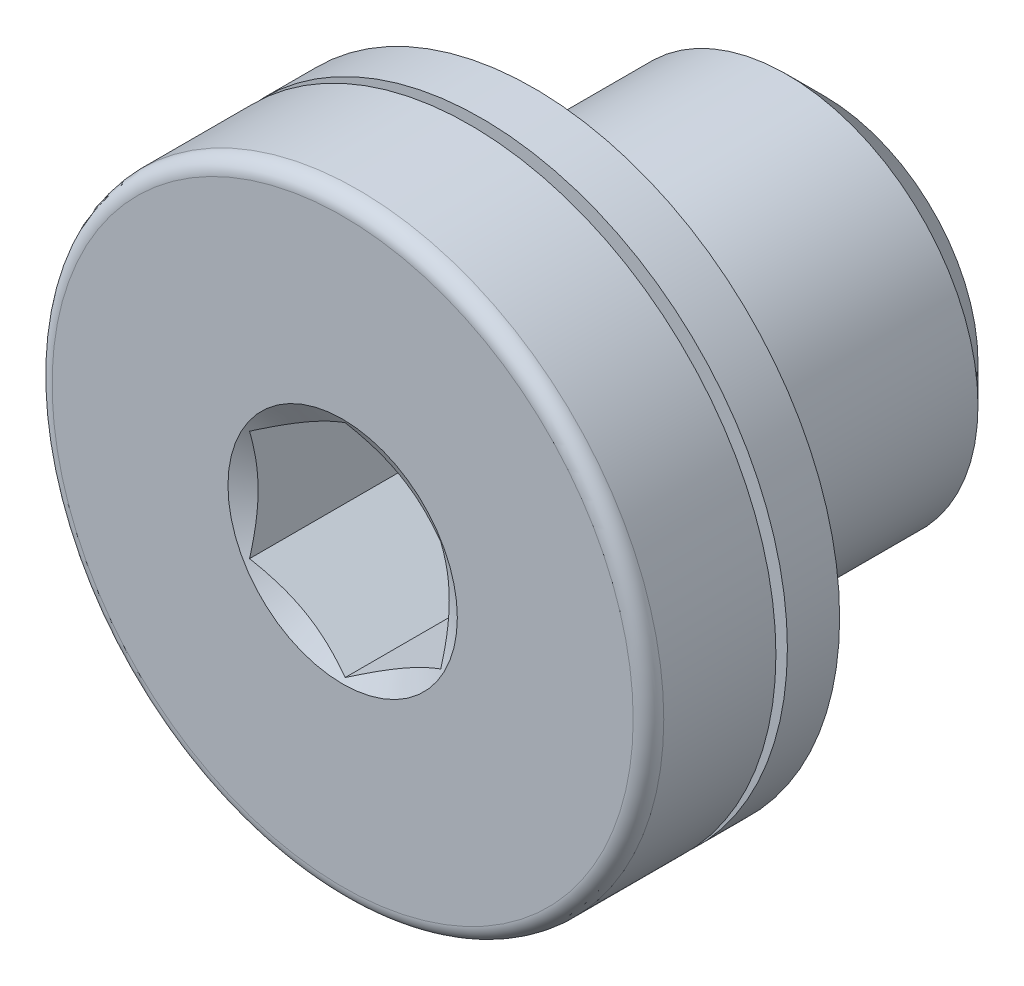
SolidWorks part; units mm, degrees
ref_plane "Ebene vorne" through (0, 0, 0) normal (0, 0, 1) x (1, 0, 0)
ref_plane "Ebene oben" through (0, 0, 0) normal (0, 1, 0) x (1, 0, 0)
ref_plane "Ebene rechts" through (0, 0, 0) normal (1, 0, 0) x (0, 0, -1)
sketch "Skizze1" plane through (0, 0, 0) normal (1, 0, 0) x (0, 0, -1)
  line L0 (-1.634, 0) -> (-2.5, 1.5)
  line L1 (-2.5, 1.5) -> (-2.5, 3.8)
  line L2 (-2.3, 4) -> (-0.8333, 4)
  line L3 (-0.8333, 4) -> (-0.8333, 3.6)
  line L4 (-0.8333, 3.6) -> (-0.6833, 3.6)
  line L5 (-0.6833, 3.6) -> (-0.6833, 4)
  line L6 (-0.6833, 4) -> (0, 4)
  line L7 (0, 4) -> (0, 2.0095)
  line L8 (0, 2.0095) -> (0.4905, 2.5)
  line L9 (0.4905, 2.5) -> (3.3095, 2.5)
  line L10 (3.3095, 2.5) -> (3.8, 2.0095)
  line L11 (3.8, 2.0095) -> (3.8, 0)
  line L12 (3.8, 0) -> (-1.634, 0)
  line L13 (3.8, 0) -> (-1.634, 0) construction
  arc A0 (-2.5, 3.8) -> (-2.3, 4) centre (-2.3, 3.8) cw
revolve "Rotation1" add sketch "Skizze1" angle 360 about L13 reverse direction yes
cosmetic thread "Gewindedarstellung1" parameters "D1"=3.8, "D2"=4.019
ref_plane "Ebene1" through (0, 0, 2.5) normal (0, 0, 1) x (1, 0, 0)
sketch "Skizze2" plane through (0, 0, 2.5) normal (0, 0, 1) x (1, 0, 0)
  line L0 (-1.25, -0.7217) -> (0, -1.4434)
  line L1 (0, -1.4434) -> (1.25, -0.7217)
  line L2 (1.25, -0.7217) -> (1.25, 0.7217)
  line L3 (1.25, 0.7217) -> (0, 1.4434)
  line L4 (0, 1.4434) -> (-1.25, 0.7217)
  line L5 (-1.25, 0.7217) -> (-1.25, -0.7217)
extrude "Schnitt-Linear austragen1" cut sketch "Skizze2" against normal blind 2.5
ref_plane "ANBAU XY" through (0, 0, 0) normal (0, 0, 1) x (1, 0, 0)
ref_plane "ANBAU XZ" through (0, 0, 0) normal (0, -1, 0) x (-1, 0, 0)
ref_plane "ANBAU YZ" through (0, 0, 0) normal (1, 0, 0) x (0, 0, -1)
ref_axis "ANBAU X" through (-80.9, 0, 0) along (1, 0, 0)
ref_axis "ANBAU Y" through (0, -50, 0) along (0, 1, 0)
ref_axis "ANBAU Z" through (0, 0, 80.9) along (0, 0, -1)
sketch3d "ANBAU"
  point P0 (0, 0, 0)
ref_plane "ANBAU_STD XY" through (0, 0, 0) normal (0, 0, 1) x (1, 0, 0)
ref_plane "ANBAU_STD XZ" through (0, 0, 0) normal (0, -1, 0) x (-1, 0, 0)
ref_plane "ANBAU_STD YZ" through (0, 0, 0) normal (1, 0, 0) x (0, 0, -1)
ref_axis "ANBAU_STD X" through (-80.9, 0, 0) along (1, 0, 0)
ref_axis "ANBAU_STD Y" through (0, -50, 0) along (0, 1, 0)
ref_axis "ANBAU_STD Z" through (0, 0, 80.9) along (0, 0, -1)
sketch3d "ANBAU_STD"
  point P0 (0, 0, 0)
